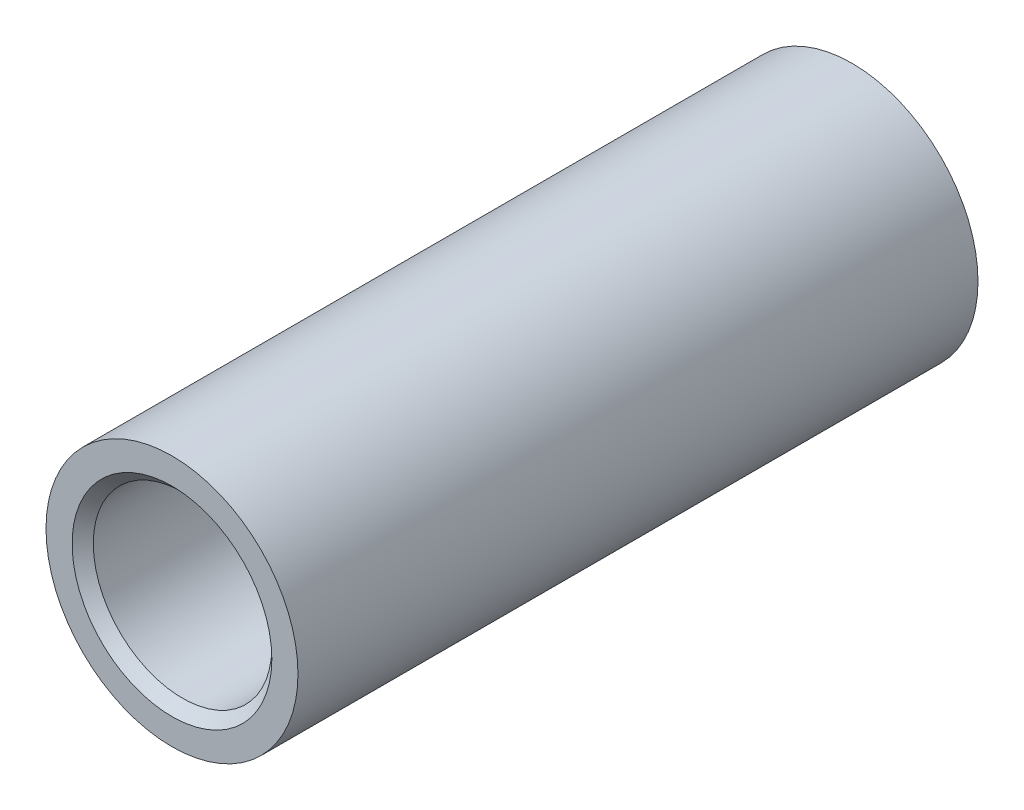
SolidWorks part; units mm, degrees
ref_plane "Front Plane" through (0, 0, 0) normal (0, 0, 1) x (1, 0, 0)
ref_plane "Top Plane" through (0, 0, 0) normal (0, 1, 0) x (1, 0, 0)
ref_plane "Right Plane" through (0, 0, 0) normal (1, 0, 0) x (0, 0, -1)
sketch "Sketch1" plane through (0, 0, 0) normal (0, 0, 1) x (1, 0, 0)
  circle A0 centre (0, 0) radius 3.375
  circle A1 centre (0, 0) radius 4.7625
  dimension "D1" = 6.75
  dimension "D2" = 9.525
extrude "Boss-Extrude1" add sketch "Sketch1" along normal blind 25.708
chamfer "Chamfer1" distance 0.4 angle 45 2 edges at (3.375, 0, 0) (3.375, 0, 25.708)
